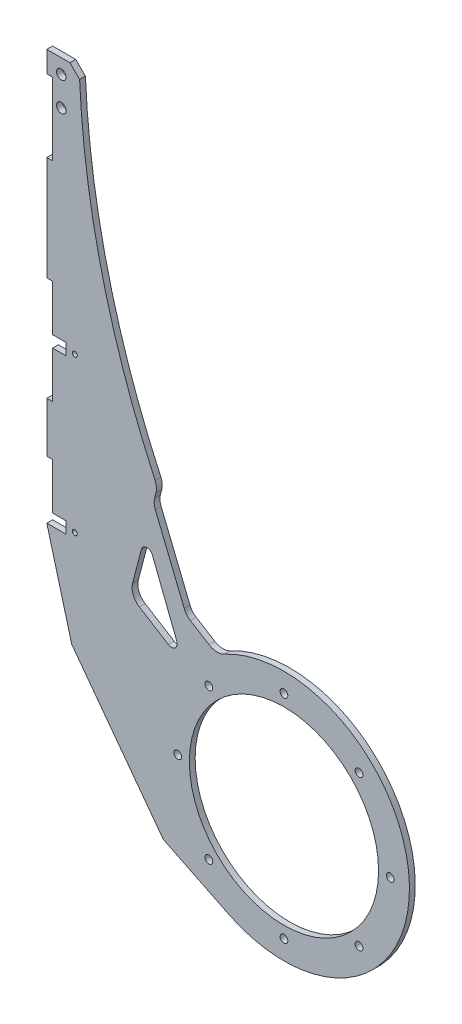
SolidWorks part; units mm, degrees
material "ABS PC"
ref_plane "Front Plane" through (0, 0, 0) normal (0, 0, 1) x (1, 0, 0)
ref_plane "Top Plane" through (0, 0, 0) normal (0, 1, 0) x (1, 0, 0)
ref_plane "Right Plane" through (0, 0, 0) normal (1, 0, 0) x (0, 0, -1)
sketch "Sketch1" plane through (0, 0, 0) normal (0, 0, 1) x (1, 0, 0)
  line L0 (-38.0629, 0.4515) -> (-37.3678, 3.1303)
  line L1 (-37.7302, -4.571) -> (-22.7201, -41.4883)
  line L2 (-83.9186, 41.25) -> (-83.9186, 47.25)
  line L3 (-83.9186, -38.75) -> (-83.9186, -32.75)
  line L4 (-93.9186, -38.75) -> (-83.9186, -38.75)
  line L5 (-93.9186, -38.75) -> (-80.9866, -86.688)
  line L6 (-83.9186, -32.75) -> (-90.9186, -32.75)
  line L7 (-90.9186, 41.25) -> (-83.9186, 41.25)
  line L8 (-83.9186, 47.25) -> (-90.9186, 47.25)
  line L9 (-90.9186, 71.25) -> (-90.9186, 47.25)
  line L10 (-93.9186, 125.25) -> (-93.9186, 71.25)
  line L11 (-93.9186, 173.75) -> (-81.9186, 173.75)
  line L12 (-93.9186, 162.75) -> (-90.9186, 162.75)
  line L13 (-80.9866, -86.688) -> (-33.6008, -150.4499)
  line L14 (-33.6008, -150.4499) -> (0.8922, -167.3975)
  line L15 (-19.5385, -45.2658) -> (-9.9113, -51.2616)
  line L16 (-90.9186, -8.75) -> (-90.9186, -32.75)
  line L17 (-93.9186, 17.25) -> (-93.9186, -8.75)
  line L18 (-93.9186, -8.75) -> (-90.9186, -8.75)
  line L19 (-93.9186, 71.25) -> (-90.9186, 71.25)
  line L20 (-93.9186, 17.25) -> (-90.9186, 17.25)
  line L21 (-90.9186, 41.25) -> (-90.9186, 17.25)
  line L22 (-93.9186, 173.75) -> (-93.9186, 162.75)
  line L23 (-90.9186, 162.75) -> (-90.9186, 125.25)
  line L24 (-93.9186, 125.25) -> (-90.9186, 125.25)
  line L25 (-44.9355, -26.034) -> (-49.4847, -43.5657)
  line L26 (-39.2376, -25.6951) -> (-26.577, -58.0771)
  line L27 (-30.957, -61.7161) -> (-45.9704, -52.3657)
  line L28 (-76.9186, 168.75) -> (-81.9186, 173.75)
  circle A0 centre (-79.4186, -35.75) radius 1.3
  circle A1 centre (-86.4186, 166.25) radius 2.5
  circle A2 centre (-86.4186, 151.25) radius 2.5
  arc A3 (0.8922, -167.3975) -> (-1.8902, -51.5152) centre (28.9186, -108.75) ccw
  circle A4 centre (28.9186, -108.75) radius 49
  circle A5 centre (-9.9723, -147.6409) radius 2
  circle A6 centre (-26.0814, -108.75) radius 2
  circle A7 centre (-9.9723, -69.8591) radius 2
  circle A8 centre (28.9186, -53.75) radius 2
  circle A9 centre (67.8095, -69.8591) radius 2
  circle A10 centre (83.9186, -108.75) radius 2
  circle A11 centre (67.8095, -147.6409) radius 2
  circle A12 centre (28.9186, -163.75) radius 2
  circle A13 centre (-79.4186, 44.25) radius 1.3
  arc A14 (-76.9186, 168.75) -> (-37.8523, 8.5023) centre (351.4847, 188.3032) ccw
  arc A15 (-49.4847, -43.5657) -> (-45.9704, -52.3657) centre (-41.7412, -45.575) ccw
  arc A16 (-39.2376, -25.6951) -> (-44.9355, -26.034) centre (-42.0317, -26.7875) ccw
  arc A17 (-30.957, -61.7161) -> (-26.577, -58.0771) centre (-29.371, -59.1695) ccw
  arc A18 (-38.0629, 0.4515) -> (-37.7302, -4.571) centre (-30.3193, -1.5579) ccw
  arc A19 (-22.7201, -41.4883) -> (-19.5385, -45.2658) centre (-15.3093, -38.4751) ccw
  arc A20 (-9.9113, -51.2616) -> (-1.8902, -51.5152) centre (-5.682, -44.4709) ccw
  arc A21 (-37.3678, 3.1303) -> (-37.8523, 8.5023) centre (-45.1113, 5.1396) ccw
extrude "Boss-Extrude1" add sketch "Sketch1" along normal blind 3
